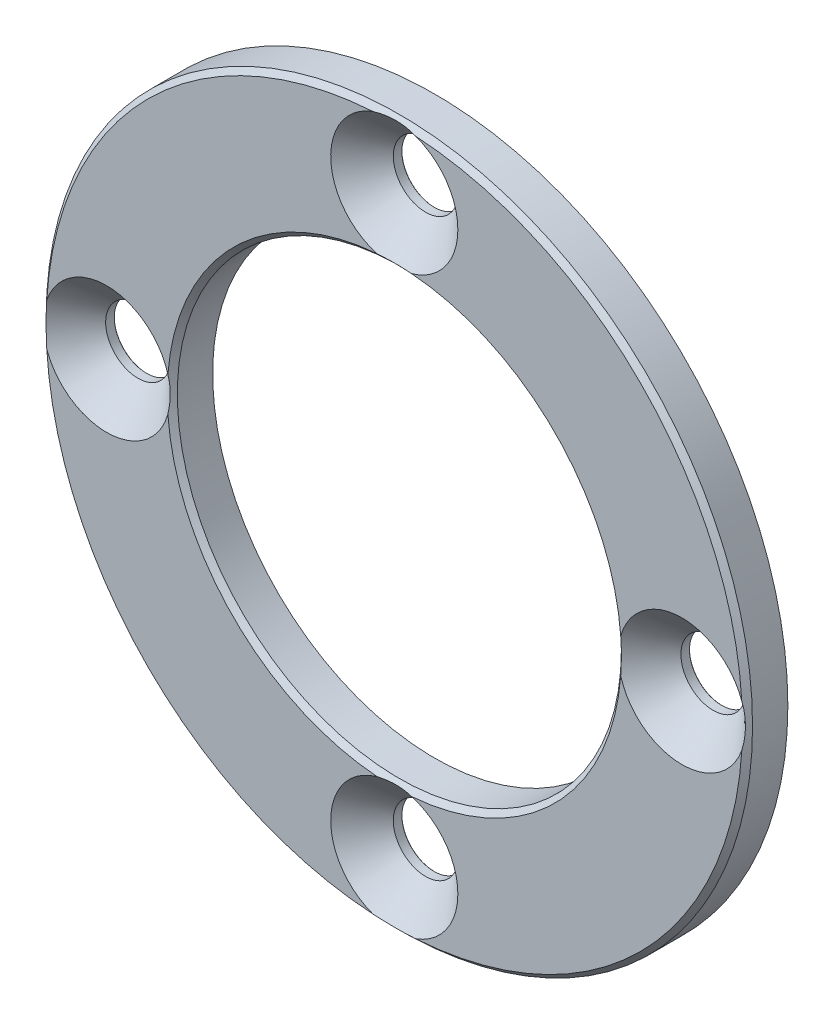
SolidWorks part; units mm, degrees
material "2018 合金"
ref_plane "正面" through (0, 0, 0) normal (0, 0, 1) x (1, 0, 0)
ref_plane "平面" through (0, 0, 0) normal (0, 1, 0) x (1, 0, 0)
ref_plane "右側面" through (0, 0, 0) normal (1, 0, 0) x (0, 0, -1)
sketch "ｽｹｯﾁ1" plane through (0, 0, 0) normal (0, 0, 1) x (1, 0, 0)
  circle A0 centre (0, 0) radius 17.5
  circle A2 centre (0, 0) radius 11
  dimension "D1" = 35
  dimension "D2" = 22
extrude "ﾎﾞｽ - 押し出し1" add sketch "ｽｹｯﾁ1" along normal blind 2
hole_wizard "M3 丸皿ねじ用皿穴1" positions "ｽｹｯﾁ3" profile "ｽｹｯﾁ4" countersink size "M3" standard "JIS" end condition through all
sketch "ｽｹｯﾁ3" plane through (0, 0, 2) normal (0, 0, 1) x (1, 0, 0)
  point P0 (0, 14.25)
  point P9 (14.25, 0)
  point P10 (0, -14.25)
  point P11 (-14.25, 0)
  point P12 (0, 0)
  dimension "D1" = 14.25
  dimension "D2" = 4
sketch "ｽｹｯﾁ4" plane through (0, 14.25, 2) normal (1, 0, 0) x (0, -1, 0)
  line L0 (0, 0) -> (0, 2)
  line L1 (0, 2) -> (1.625, 2)
  line L2 (1.6, 1.975) -> (1.6, 1.55)
  line L3 (1.6, 1.55) -> (3.15, 0)
  line L5 (3.15, 0) -> (0, 0)
  line L6 (-1.6, 1.55) -> (-3.15, 0) construction
  line L7 (1.625, 2) -> (1.6, 1.975)
  line L8 (-1.625, 2) -> (-1.6, 1.975) construction
  line L11 (0, -6.35) -> (0, 107.95) construction
  dimension "通し穴の直径" = 3.2
  dimension "通し穴の深さ" = 2
  dimension "表面の皿穴の直径" = 6.3
  dimension "表面の皿穴の角度" = 90
  dimension "裏面の皿穴の直径" = 3.25
  dimension "裏面の皿穴の角度" = 90
chamfer "面取り1" distance 0.25 angle 45 2 edges at (17.5, 0, 2) (11, 0, 2)
